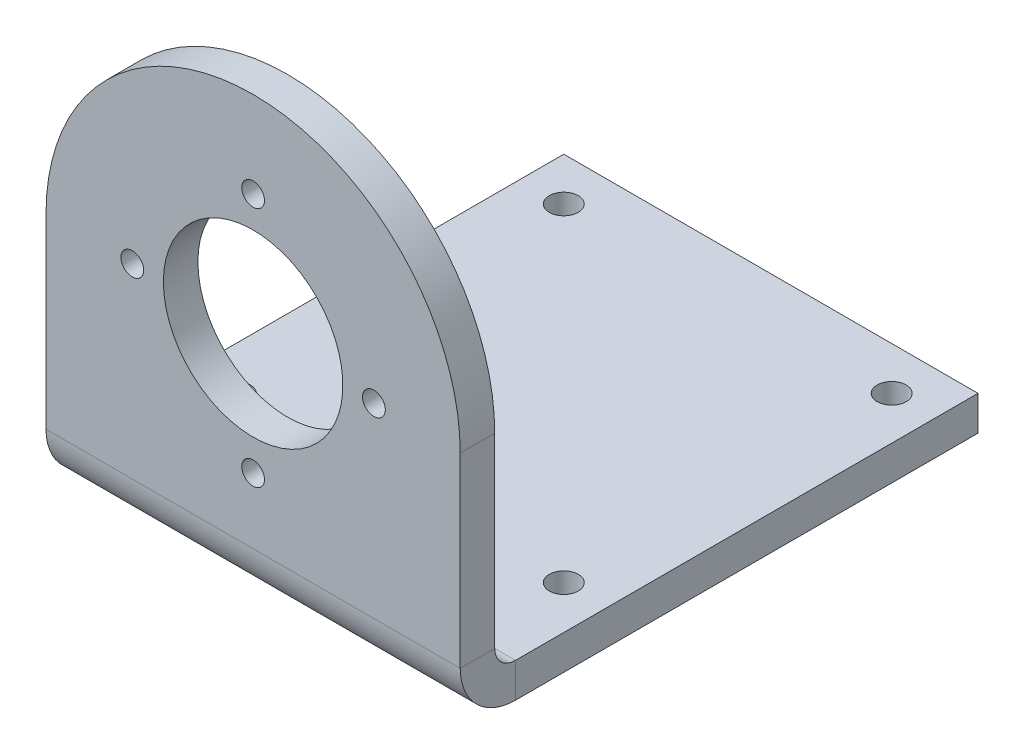
SolidWorks part; units mm, degrees
note: The reader was unsure of these and kept them because the rebuilt part matched: flange length of "边线-法兰2".
ref_plane "前视基准面" through (0, 0, 0) normal (0, 0, 1) x (1, 0, 0)
ref_plane "上视基准面" through (0, 0, 0) normal (0, 1, 0) x (1, 0, 0)
ref_plane "右视基准面" through (0, 0, 0) normal (1, 0, 0) x (0, 0, -1)
other "Configuration Table"
sketch "草图10" plane through (0, 0, 0) normal (0, 0, 1) x (1, 0, 0)
  line L1 (-30, -30) -> (30, -30)
  line L2 (-30, -30) -> (-30, 30)
  line L3 (-30, 30) -> (30, 30)
  line L4 (30, -30) -> (30, 30)
  line L5 (-30, -30) -> (30, 30) construction
  line L6 (-30, 30) -> (30, -30) construction
  point P0 (0, 0)
  dimension "D1" = 60
  dimension "D2" = 60
base flange "基体-法兰2" sketch "草图10" thickness 5 reverse thickness direction no parameters "D1"=0.7366
edge flange "边线-法兰2" sketch "草图17" flange angle 90 flange length 75 flange position material outside bend radius 3 thickness 5 relief rectangular parameters "D6"=10
sketch "草图17" plane through (0, -30, -5) normal (0, 1, 0) x (1, 0, 0)
  line L2 (-30, 0) -> (-30, 70)
  line L3 (-30, 70) -> (30, 70)
  line L4 (30, 70) -> (30, 0)
  line L5 (30, 0) -> (-30, 0) construction
  line L6 (30, 0) -> (-30, 0)
  dimension "D1" = 70
bend "边线折弯2" bend radius 3 bend angle 90 parameters "D5"=1
sketch "草图19" plane through (0, 0, 0) normal (0, 0, 1) x (1, 0, 0)
  line L0 (-1000, 0) -> (49000, 0) construction
  line L1 (0, -1000) -> (0, 49000) construction
  circle A0 centre (0, 0) radius 17.5 construction
  circle A1 centre (-17.5, 0) radius 1.65
  circle A2 centre (17.5, 0) radius 1.65
  circle A3 centre (0, 17.5) radius 1.65
  circle A4 centre (0, -17.5) radius 1.65
  circle A5 centre (0, 0) radius 13
  dimension "D1" = 35
  dimension "D2" = 3.3
  dimension "D3" = 3.3
  dimension "D4" = 3.3
  dimension "D5" = 3.3
  dimension "D6" = 26
extrude "切除-拉伸2" cut sketch "草图19" against normal up to surface (5 mm away) from surface at 0 up to face at (0, 1.5, -5) starting at face at (0, 1.5, 0)
sketch "草图28" plane through (0, 0, 0) normal (0, 1, 0) x (1, 0, 0)
  line L0 (30, 8) -> (30, 75) construction
  line L1 (-30, 75) -> (30, 75) construction
  line L2 (-30, 75) -> (-30, 15) construction
  line L3 (-30, 15) -> (30, 15) construction
  line L4 (30, 75) -> (30, 15) construction
  line L5 (-30, 75) -> (30, 15) construction
  line L6 (30, 75) -> (-30, 15) construction
  line L8 (-23.75, 21.25) -> (23.75, 21.25) construction
  line L9 (-23.75, 21.25) -> (-23.75, 68.75) construction
  line L10 (-23.75, 68.75) -> (23.75, 68.75) construction
  line L11 (23.75, 21.25) -> (23.75, 68.75) construction
  line L12 (-23.75, 21.25) -> (23.75, 68.75) construction
  line L13 (-23.75, 68.75) -> (23.75, 21.25) construction
  circle A0 centre (-23.75, 21.25) radius 2.1
  circle A1 centre (-23.75, 68.75) radius 2.1
  circle A2 centre (23.75, 68.75) radius 2.1
  circle A3 centre (23.75, 21.25) radius 2.1
  point P7 (0, 45)
  dimension "D4" = 4.2
  dimension "D5" = 4.2
  dimension "D6" = 4.2
  dimension "D7" = 4.2
  dimension "D1" = 60
  dimension "D2" = 47.5
  dimension "D3" = 47.5
extrude "切除-拉伸4" cut sketch "草图28" against normal up to surface (5 mm away) from surface at -30 up to face at (0, -35, -41.5) starting at face at (0, -30, -41.5)
sketch "草图29" plane through (0, 0, 0) normal (0, 0, 1) x (1, 0, 0)
  line L1 (0, 30) -> (-30, 30)
  line L4 (-30, 30) -> (-30, 0)
  line L6 (0, 30) -> (30, 30)
  line L9 (30, 30) -> (30, 0)
  arc A0 (30, 0) -> (-30, 0) centre (0, 0) ccw
  dimension "D1" = 60
extrude "切除-拉伸5" cut sketch "草图29" against normal up to surface (5 mm away) from surface at 0 contours A0 L1 L4 | A0 L9 L6 up to face at (-19.15, 0, -5) starting at face at (-19.15, 0, 0)
sketch "折弯-线3" plane through (0, 0, 0) normal (0, 1, 0) x (1, 0, 0)
sketch "边界框3" plane through (0, 0, 0) normal (0, 1, 0) x (1, 0, 0)
sheet metal parameters "钣金9" thickness 5 parameters "D1"=0.7366
flat pattern "平板型式9" [suppressed]
sketch "折弯-线4" plane through (0, 0, 0) normal (0, 1, 0) x (1, 0, 0)
sketch "边界框4" [suppressed] plane through (0, 0, 0) normal (0, 1, 0) x (1, 0, 0)
sheet metal parameters "钣金10" thickness 5 parameters "D1"=0.7366
flat pattern "平板型式9" [suppressed]
sketch "折弯-线4" plane through (0, 0, 0) normal (0, 1, 0) x (1, 0, 0)
sketch "边界框4" [suppressed] plane through (0, 0, 0) normal (0, 1, 0) x (1, 0, 0)
bend of the flat pattern "展平-<边线折弯2>1"
sheet metal parameters "钣金11" thickness 5 parameters "D1"=0.7366
flat pattern "平板型式9" [suppressed]
sketch "折弯-线4" plane through (0, 0, 0) normal (0, 1, 0) x (1, 0, 0)
sketch "边界框4" [suppressed] plane through (0, 0, 0) normal (0, 1, 0) x (1, 0, 0)
bend of the flat pattern "展平-<边线折弯2>1"
sheet metal parameters "钣金14" thickness 5 parameters "D1"=0.7366
flat pattern "平板型式9" [suppressed]
sketch "折弯-线4" plane through (0, 0, 0) normal (0, 1, 0) x (1, 0, 0)
sketch "边界框4" [suppressed] plane through (0, 0, 0) normal (0, 1, 0) x (1, 0, 0)
bend of the flat pattern "展平-<边线折弯2>1"
sheet metal parameters "钣金15" thickness 5 parameters "D1"=0.7366
flat pattern "平板型式9" [suppressed]
sketch "折弯-线4" plane through (0, 0, 0) normal (0, 1, 0) x (1, 0, 0)
sketch "边界框4" [suppressed] plane through (0, 0, 0) normal (0, 1, 0) x (1, 0, 0)
bend of the flat pattern "展平-<边线折弯2>1"
